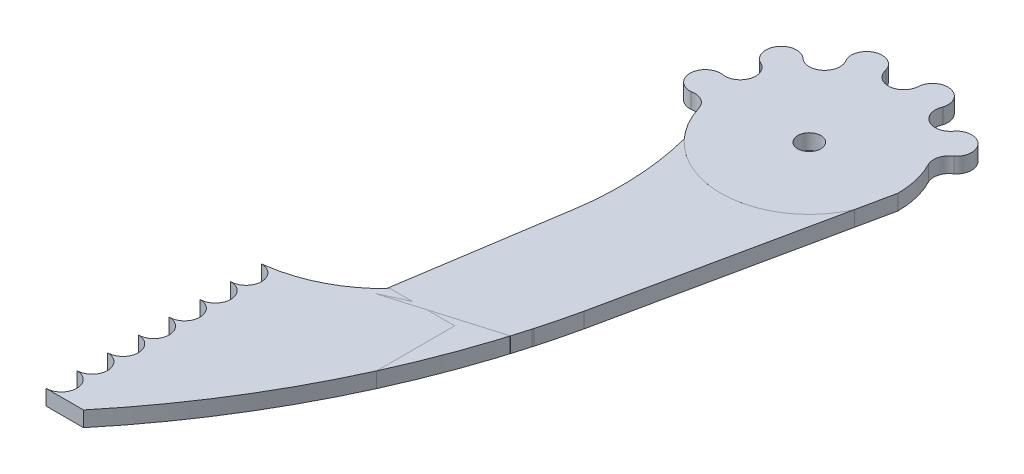
SolidWorks part; units mm, degrees
note: The reader was unsure of these and kept them because the rebuilt part matched: shared geometry of "Sketch1<5>", "Sketch2<5>".
ref_plane "Front Plane" through (0, 0, 0) normal (0, 0, 1) x (1, 0, 0)
ref_plane "Top Plane" through (0, 0, 0) normal (0, 1, 0) x (1, 0, 0)
ref_plane "Right Plane" through (0, 0, 0) normal (1, 0, 0) x (0, 0, -1)
sketch "Sketch1" plane through (0, 0, 0) normal (0, 1, 0) x (1, 0, 0)
  line L0 (0, 0) -> (-13.5, 0) construction
  line L1 (0, 0) -> (11.5, 0) construction
  line L2 (11.5, 0) -> (2.8068, -41.0887)
  line L3 (2.8068, -41.0887) -> (-11.192, -45.2316)
  line L4 (-11.192, -45.2316) -> (-7.7384, -22.8541)
  circle A0 centre (0, 0) radius 11.5
  circle A4 centre (-13.5, 0) radius 2
  circle A5 centre (-12.9101, 3.947) radius 2
  circle A6 centre (-11.192, 7.5491) radius 2
  circle A7 centre (-8.4958, 10.4915) radius 2
  circle A8 centre (-5.0572, 12.517) radius 2
  circle A9 centre (-1.1766, 13.4486) radius 2
  circle A10 centre (2.8068, 13.205) radius 2
  circle A11 centre (6.5449, 11.8074) radius 2
  circle A12 centre (9.7111, 9.3779) radius 2
  circle A13 centre (12.0286, 6.1289) radius 2
  circle A14 centre (13.2949, 2.3443) radius 2
  arc A15 (-7.7384, -22.8541) -> (-8.4958, -7.7505) centre (-44.7626, -17.14) ccw
  circle A16 centre (0, 0) radius 1.5
  circle A17 centre (-12.9126, -3.9389) radius 2
  circle A18 centre (-11.1966, -7.5423) radius 2
  point P38 (0, 0)
  dimension "D1" = 23
  dimension "D2" = 4
  dimension "D4" = 13.5
  dimension "D5" = 3
  dimension "D3" = 11
extrude "Boss-Extrude3" add sketch "Sketch1" along normal mid plane 2
extrude "Boss-Extrude5" add sketch "Sketch1<5>" along normal mid plane 2 contours A15 L4 L3 L2 A0
sketch "Sketch1<5>" plane through (0, 0, 0) normal (0, 1, 0) x (1, 0, 0) same geometry as "Sketch1"
sketch "Sketch2" plane through (0, 0, 0) normal (0, 1, 0) x (1, 0, 0)
  line L0 (-21.8888, -75.271) -> (-21.8888, -71.271) construction
  line L1 (-2.3714, -43.697) -> (-21.8888, -43.697)
  line L2 (-2.3714, -43.697) -> (-2.3714, -77.271)
  line L3 (-2.3714, -77.271) -> (-21.8888, -77.271)
  line L4 (-21.8888, -43.697) -> (-21.8888, -77.271)
  line L5 (-2.3714, -43.697) -> (-21.8888, -77.271) construction
  line L6 (-2.3714, -77.271) -> (-21.8888, -43.697) construction
  line L7 (-2.3714, -72.6671) -> (3.3843, -38.7321)
  line L8 (3.3843, -38.7321) -> (-10.7531, -43.697)
  arc A0 (-21.8888, -77.271) -> (-2.3714, -72.6671) centre (-17.022, -54.2312) ccw
  circle A1 centre (-21.8888, -75.271) radius 2
  circle A2 centre (-21.8888, -71.271) radius 2
  circle A3 centre (-21.8888, -67.271) radius 2
  circle A4 centre (-21.8888, -63.271) radius 2
  circle A5 centre (-21.8888, -59.271) radius 2
  circle A6 centre (-21.8888, -55.271) radius 2
  circle A7 centre (-21.8888, -51.271) radius 2
  circle A8 centre (-21.8888, -47.271) radius 2
  arc A9 (-21.8888, -49.271) -> (-10.7531, -43.697) centre (-23.9653, -31.2122) ccw
  point P0 (-12.1301, -60.484)
  dimension "D1" = 4
  dimension "D3" = 4
  dimension "D2" = 8
extrude "Boss-Extrude7" add sketch "Sketch2" along normal mid plane 2 contours A9 A8 A7 A6 A5 A4 A3 A2 A1 L3 A0 L2 L1
extrude "Boss-Extrude8" add sketch "Sketch2<5>" along normal mid plane 2 contours L7 L8 L1 L2
sketch "Sketch2<5>" plane through (0, 0, 0) normal (0, 1, 0) x (1, 0, 0) same geometry as "Sketch2"
sketch "Sketch3" plane through (0, 0, 0) normal (0, 1, 0) x (1, 0, 0)
  line L0 (-12.1551, -77.271) -> (-21.8888, -77.271) construction
  line L1 (10.5146, -4.6577) -> (2.8068, -41.0887) construction
  line L2 (-17.022, -77.271) -> (4.8916, -77.271)
  line L3 (4.8916, -77.271) -> (4.8916, -31.235)
  arc A0 (-17.022, -77.271) -> (4.8916, -31.235) centre (-97.1506, -10.8956) ccw
extrude "Cut-Extrude2" cut sketch "Sketch3" against normal mid plane 2 contours L3 A0 L2
